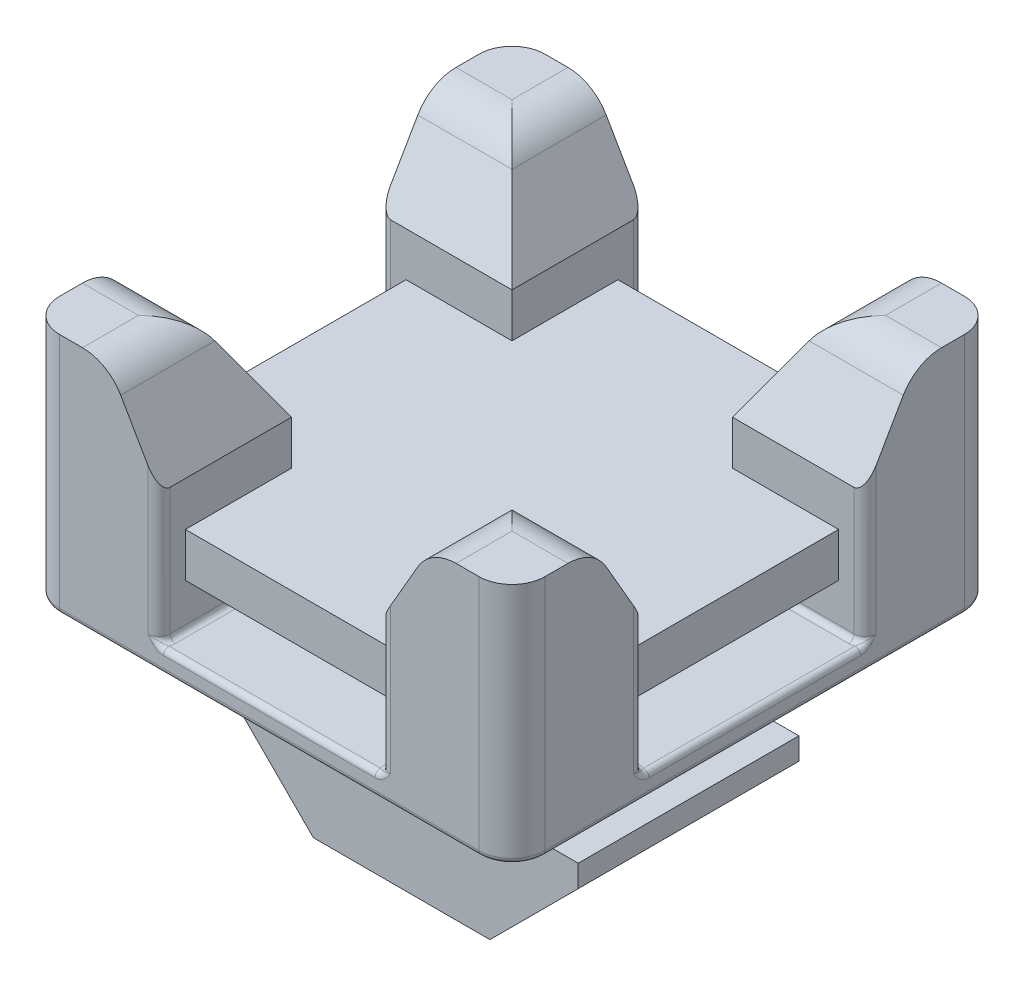
SolidWorks part; units mm, degrees
note: The reader was unsure of these and kept them because the rebuilt part matched: shared geometry of "Sketch5<3>".
other "Imported1" parameters "D2"=26.8126, "D3"=5.2339, "D5"=74.6687, "D8"=40.6466, "D9"=74.6687, "D4"=2.9052, "D1"=4, "D6"=2.918, "D7"=7.3167, "D10"=5.3786, "D11"=2.788, "D12"=2.788, "D13"=2.788, "D14"=3.4743, "Cable Tie Length"=200, "Cable Tie Width"=8
ref_plane "Front Plane" through (0, 0, 0) normal (0, 0, 1) x (1, 0, 0)
ref_plane "Top Plane" through (0, 0, 0) normal (0, 1, 0) x (1, 0, 0)
ref_plane "Right Plane" through (0, 0, 0) normal (1, 0, 0) x (0, 0, -1)
sketch "Sketch7" plane through (0, 0, 0) normal (0, 1, 0) x (1, 0, 0)
  line L1 (11, -11) -> (-11, -11)
  line L2 (11, -11) -> (11, 11)
  line L3 (11, 11) -> (-11, 11)
  line L4 (-11, -11) -> (-11, 11)
  line L5 (11, -11) -> (-11, 11) construction
  line L6 (11, 11) -> (-11, -11) construction
  point P0 (0, 0)
  dimension "Square Size" = 22
sketch "Sketch8" plane through (0, 0, 0) normal (0, 0, 1) x (1, 0, 0)
  line L0 (11, -10) -> (11, 10) construction
  line L1 (-5, 0) -> (5, 0) construction
  line L2 (4, -5) -> (-4, -5) construction
  line L4 (-11, 0) -> (-11, 2) construction
  line L5 (11, 0) -> (-11, 0) construction
  line L6 (11, 0) -> (-11, 0) construction
  circle A0 centre (0, 27) radius 25 construction
  point P3 (11, 0)
  point P10 (11, -5)
  point P12 (11, -1)
  point P16 (0, 0)
  point P17 (-11, 1.5)
  point P19 (-11, 2)
  point P22 (0, 2)
  point P23 (11, -10)
  point P25 (0, -5)
  point P27 (-4, -5)
  point P28 (4, -5)
  dimension "For Maximum Bundle Diameter" = 50
  dimension "Height" = 20
  dimension "For Maximum Cable Tie Thickness" = 2
  dimension "Stem Height" = 4
  dimension "Head Height" = 11
  dimension "Cable Channel Width" = 10
  dimension "Actual Cable Tie Height" = 1.5
  dimension "Stem Width" = 8
sketch "Sketch9" plane through (0, 0, 0) normal (0, 1, 0) x (1, 0, 0)
  line L0 (-100, 0) -> (100, 0) construction
  line L1 (-100, 4) -> (-100, -4) construction
  point P3 (0, 0)
  point P6 (-100, 0)
sketch "Sketch15" plane through (0, 0, 0) normal (1, 0, 0) x (0, 0, -1)
  line L0 (-5, -10) -> (5, -10) construction
  line L2 (0, -10) -> (0, 10) construction
  point P4 (0, -10)
  point P7 (-5, -10)
  point P8 (5, -10)
  dimension "Nose width" = 10
sketch "Sketch1" plane through (0, 0, 0) normal (0, 1, 0) x (1, 0, 0)
  line L0 (-11, 0) -> (11, 0) construction
  line L1 (-11, 11) -> (11, 11)
  line L2 (-11, 11) -> (-11, -11)
  line L3 (-11, -11) -> (11, -11)
  line L4 (11, 11) -> (11, -11)
  line L5 (0, 11) -> (0, -11) construction
extrude "Boss-Extrude1" add sketch "Sketch1" along normal up to vertex (10 mm away) from vertex at -1 starting at point (11, -1, 0)
sketch "Sketch2" plane through (0, 0, 0) normal (0, 1, 0) x (1, 0, 0)
  line L0 (5, -5) -> (5, -11)
  line L1 (-11, 5) -> (-5, 5)
  line L2 (-11, 5) -> (-11, -5)
  line L3 (-11, -5) -> (-5, -5)
  line L4 (11, 5) -> (11, -5)
  line L5 (-5, 11) -> (5, 11)
  line L6 (-5, 11) -> (-5, 5)
  line L7 (-5, -11) -> (5, -11)
  line L8 (5, 11) -> (5, 5)
  line L9 (5, -5) -> (11, -5)
  line L10 (-5, -5) -> (-5, -11)
  line L11 (5, 5) -> (11, 5)
  dimension "D1" = 10
  dimension "D2" = 10
  dimension "D3" = 6
extrude "Cut-Extrude1" cut sketch "Sketch2" along normal through all draft 30 from offset 6
sketch "Sketch3" plane through (0, 0, 0) normal (0, 1, 0) x (1, 0, 0)
  line L12 (5, -11) -> (5, -5)
  line L13 (-5, -11) -> (5, -11)
  line L14 (-5, -5) -> (-5, -11)
  line L15 (-11, -5) -> (-5, -5)
  line L16 (-11, 5) -> (-11, -5)
  line L17 (-5, 5) -> (-11, 5)
  line L18 (-5, 11) -> (-5, 5)
  line L19 (5, 11) -> (-5, 11)
  line L20 (5, 5) -> (5, 11)
  line L21 (11, 5) -> (5, 5)
  line L22 (11, -5) -> (11, 5)
  line L23 (5, -5) -> (11, -5)
  line L24 (5, -11) -> (5, -5)
  line L25 (-5, -11) -> (5, -11)
  line L26 (-5, -5) -> (-5, -11)
  line L27 (-11, -5) -> (-5, -5)
  line L28 (-11, 5) -> (-11, -5)
  line L29 (-5, 5) -> (-11, 5)
  line L30 (-5, 11) -> (-5, 5)
  line L31 (5, 11) -> (-5, 11)
  line L32 (5, 5) -> (5, 11)
  line L33 (11, 5) -> (5, 5)
  line L34 (11, -5) -> (11, 5)
  line L35 (5, -5) -> (11, -5)
  dimension "D1" = 0
extrude "Cut-Extrude4" cut sketch "Sketch3" along normal up to vertex (2 mm away) up to point (-11, 2, 0)
sketch "Sketch4" plane through (0, 0, 0) normal (0, 1, 0) x (1, 0, 0)
  line L1 (-5, 11) -> (5, 11)
  line L2 (-5, 11) -> (-5, 9.8)
  line L3 (-5, 9.8) -> (5, 9.8)
  line L4 (5, 11) -> (5, 9.8)
  line L5 (-11, 5) -> (-9.8, 5)
  line L6 (-11, 5) -> (-11, -5)
  line L7 (-11, -5) -> (-9.8, -5)
  line L8 (-9.8, 5) -> (-9.8, -5)
  line L9 (-5, -11) -> (5, -11)
  line L10 (-5, -11) -> (-5, -9.8)
  line L11 (-5, -9.8) -> (5, -9.8)
  line L12 (5, -11) -> (5, -9.8)
  line L13 (11, 5) -> (9.8, 5)
  line L14 (11, 5) -> (11, -5)
  line L15 (11, -5) -> (9.8, -5)
  line L16 (9.8, 5) -> (9.8, -5)
  dimension "D1" = 1.2
  dimension "D2" = 19.6
extrude "Cut-Extrude3" cut sketch "Sketch4" along normal through all
sketch "Sketch13" plane through (0, 0, 0) normal (0, 1, 0) x (1, 0, 0)
  line L12 (5, -5) -> (11, -5)
  line L13 (5, 11) -> (-5, 11)
  line L14 (11, 5) -> (5, 5)
  line L15 (5, 5) -> (5, 11)
  line L16 (5, 11) -> (-5, 11)
  line L17 (-5, 11) -> (-5, 5)
  line L18 (-5, 5) -> (-11, 5)
  line L19 (-11, 5) -> (-11, -5)
  line L20 (-11, -5) -> (-5, -5)
  line L21 (-5, -5) -> (-5, -11)
  line L22 (-11, 5) -> (-11, -5)
  line L23 (5, -11) -> (5, -5)
  line L24 (5, -5) -> (11, -5)
  line L26 (11, 5) -> (5, 5)
  line L27 (5, 5) -> (5, 11)
  line L29 (-5, 11) -> (-5, 5)
  line L30 (-5, 5) -> (-11, 5)
  line L32 (-11, -5) -> (-5, -5)
  line L33 (-5, -5) -> (-5, -11)
  line L35 (5, -11) -> (5, -5)
  line L36 (-5, -11) -> (5, -11)
  line L37 (-5, -11) -> (5, -11)
  line L38 (11, -5) -> (11, 5)
  line L39 (11, -5) -> (11, 5)
  dimension "D1" = 0
extrude "Cut-Extrude5" cut sketch "Sketch13" against normal blind 2 from surface at 6 starting at face at (0, 6, 0)
fillet "Fillet1" radius 1.5 4 edges at (-11, 4.5, 11) (11, 4.5, 11) (11, 4.5, -11) (-11, 4.5, -11)
fillet "Fillet2" radius 0.5 8 edges at (11, 3, -5) (11, 3, 5) (5, 3, 11) (-5, 3, 11) (-11, 3, 5) (-11, 3, -5) (5, 3, -11) (-5, 3, -11)
fillet "Fillet3" radius 2 8 edges at (7.3094, 10, 9.1547) (9.1547, 10, 7.3094) (9.1547, 10, -7.3094) (7.3094, 10, -9.1547) (-7.3094, 10, -9.1547) (-9.1547, 10, -7.3094) (-9.1547, 10, 7.3094) (-7.3094, 10, 9.1547)
fillet "Fillet5" radius 0.25 28 edges at (10.5607, -1, 10.5607) (11, -1, 0) (10.5607, -1, -10.5607) (0, -1, -11) (-10.5607, -1, -10.5607) (-11, -1, 0) (-10.5607, -1, 10.5607) (0, -1, 11) (10.8536, 0, 5.1464) (7.75, 0, 5) (5, 0, 7.75) (5.1464, 0, 10.8536) (0, 0, 11) (-5.1464, 0, 10.8536) (-5, 0, 7.75) (-7.75, 0, 5) (-10.8536, 0, 5.1464) (-11, 0, 0) (-10.8536, 0, -5.1464) (-7.75, 0, -5) (-5, 0, -7.75) (-5.1464, 0, -10.8536) (0, 0, -11) (5.1464, 0, -10.8536) (5, 0, -7.75) (7.75, 0, -5) (10.8536, 0, -5.1464) (11, 0, 0)
sketch "Sketch5" plane through (0, 0, 0) normal (0, 0, 1) x (1, 0, 0)
  line L0 (0, -1) -> (0, -10) construction
  line L1 (5, -1) -> (-5, -1) construction
  line L2 (4, -10) -> (-4, -10)
  line L3 (8, -6) -> (4, -10)
  line L4 (-8, -5) -> (-4, -5)
  line L5 (-4, -5) -> (-4, -1)
  line L6 (-4, -1) -> (4, -1)
  line L7 (4, -5) -> (4, -1)
  line L8 (8, -5) -> (4, -5)
  line L9 (8, -5) -> (8, -6)
  line L10 (-8, -5) -> (-8, -6)
  line L11 (-8, -6) -> (-4, -10)
  line L12 (-4, -5) -> (4, -5)
  point P15 (4, -3)
  dimension "D1" = 1
  dimension "D4" = 16
  dimension "D6" = 45
extrude "Boss-Extrude2" add sketch "Sketch5" along normal up to vertex (5 mm away) and the other way up to vertex (5 mm away) contours L0 L6 L5 L12 | L6 L0 L12 L7 up to point (0, -10, 5) other way up to point (0, -10, -5)
extrude "Boss-Extrude3" add sketch "Sketch5<3>" along normal up to vertex (5 mm away) and the other way up to vertex (5 mm away) contours L12 L0 L2 L3 L9 L8 | L0 L12 L4 L10 L11 L2 up to point (0, -10, 5) other way up to point (0, -10, -5)
sketch "Sketch5<3>" plane through (0, 0, 0) normal (0, 0, 1) x (1, 0, 0) same geometry as "Sketch5"
fillet "Fillet4" radius 2 4 edges
sketch "Sketch14" plane through (0, 0, 0) normal (0, 1, 0) x (1, 0, 0)
  line L0 (-100, 0) -> (100, 0) construction
  line L1 (-100, 4) -> (100, 4) construction
  line L2 (-100, 4) -> (-100, -4) construction
  line L3 (-100, -4) -> (100, -4) construction
  line L4 (100, 4) -> (100, -4) construction
  line L5 (-96, 0) -> (-93.1716, 2.8284) construction
  line L6 (-96, 0) -> (-96, 4) construction
  line L9 (-96, 0) -> (-96, -4) construction
  line L10 (-93.1716, -2.8284) -> (-96, 0) construction
  line L13 (100, 9.498) -> (100, 2.8284) construction
  line L14 (100, 2.8284) -> (97.212, 1.7372) construction
  line L15 (97.212, 1.7372) -> (97.212, -1.7372) construction
  line L16 (97.212, -1.7372) -> (100, -2.8284) construction
  line L17 (100, -2.8284) -> (100, -9.498) construction
  line L18 (89.8953, 4) -> (89.8953, -4) construction
  line L19 (91.2703, 4) -> (91.2703, -4)
  line L20 (88.5203, 4) -> (88.5203, -4)
  line L21 (78, 4) -> (-75.1963, 4)
  line L22 (-75.1963, -4) -> (78, -4)
  line L23 (100, 9.498) -> (100, 2.8284)
  line L24 (100, 2.8284) -> (97.212, 1.7372)
  line L25 (97.212, 1.7372) -> (97.212, -1.7372)
  line L26 (97.212, -1.7372) -> (100, -2.8284)
  line L27 (100, -2.8284) -> (100, -9.498)
  circle A0 centre (-96, 0) radius 4 construction
  arc A1 (-100, 0) -> (-93.1716, 2.8284) centre (-96, 0) cw
  arc A2 (-90.3909, 2.0698) -> (-93.1716, 2.8284) centre (-91.1173, 4.8827) cw
  arc A3 (-100, 0) -> (-93.1716, -2.8284) centre (-96, 0) ccw
  arc A4 (-90.3909, 2.0698) -> (-75.1963, 4) centre (-75.1963, -56.7705) cw
  arc A5 (-93.1716, -2.8284) -> (-90.3909, -2.0698) centre (-91.1173, -4.8827) cw
  arc A6 (-90.3909, -2.0698) -> (-75.1963, -4) centre (-75.1963, 56.7705) ccw
  arc A7 (100, 9.498) -> (84.188, 6.2964) centre (100, -31.1486) ccw
  arc A8 (84.188, 6.2964) -> (78, 4) centre (55.1411, 75.0837) cw
  arc A9 (100, -9.498) -> (84.188, -6.2964) centre (100, 31.1486) cw
  arc A10 (84.188, -6.2964) -> (78, -4) centre (55.1411, -75.0837) ccw
  arc A11 (91.2703, 4) -> (88.5203, 4) centre (89.8953, 4) ccw
  arc A12 (88.5203, -4) -> (91.2703, -4) centre (89.8953, -4) ccw
  point P5 (100, 0)
  point P11 (-92, 0)
  point P30 (97.212, 0)
  point P40 (89.8953, 0)
  dimension "D5" = 74.6687
  dimension "D8" = 40.6466
  dimension "D3" = 60.7705
  dimension "D4" = 2.9052
  dimension "D6" = 2.75
  dimension "D7" = 7.3167
  dimension "D9" = 18.9959
  dimension "D10" = 22
  dimension "D11" = 21.376
  dimension "D12" = 21.376
  dimension "D13" = 2.788
  dimension "D14" = 3.4743
  dimension "D2" = 90
ref_plane "Contact Plane 1" through (0, -1, 0) normal (0, 1, 0) x (1, 0, 0)
ref_plane "Contact Plane 2" through (0, -5, 0) normal (0, 1, 0) x (1, 0, 0)
ref_plane "Contact Plane 3" through (4, 0, 0) normal (1, 0, 0) x (0, 0, -1)
ref_plane "Contact Plane 4" through (-4, 0, 0) normal (-1, 0, 0) x (0, 0, 1)
equation "\"D10@Sketch14\"=\"Cable Tie Length@Sketch9\"*.11"
